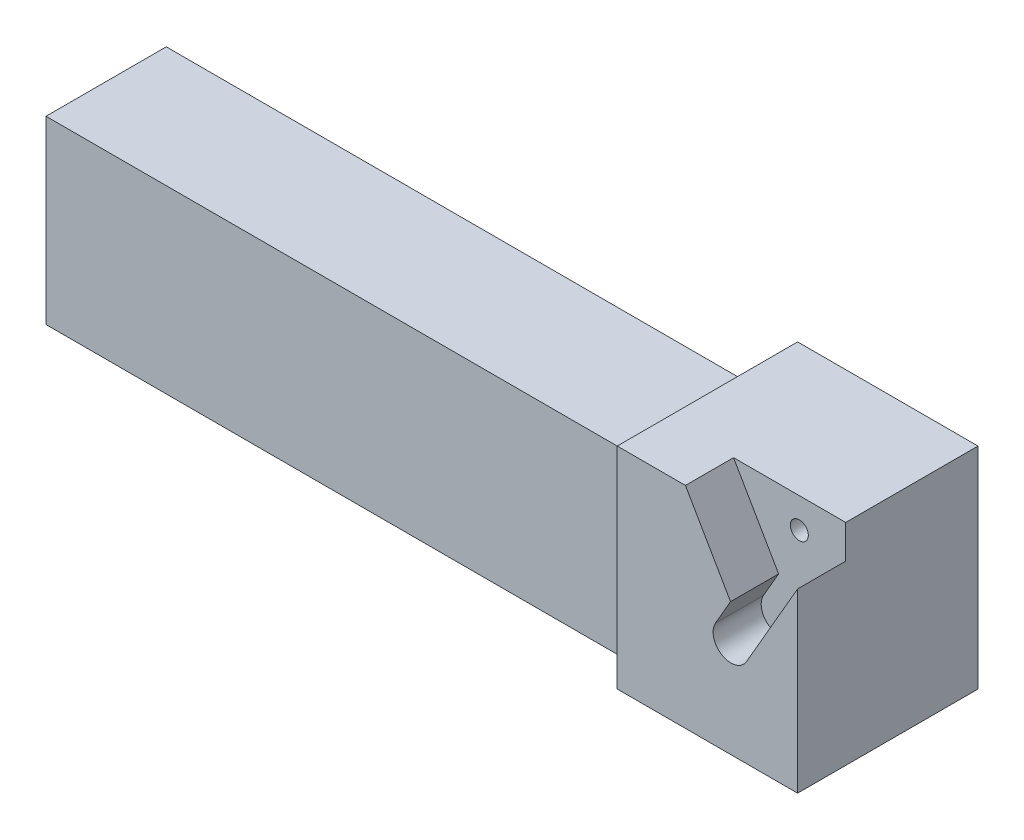
SolidWorks part; units mm, degrees
ref_plane "前视基准面" through (0, 0, 0) normal (0, 0, 1) x (1, 0, 0)
ref_plane "上视基准面" through (0, 0, 0) normal (0, 1, 0) x (1, 0, 0)
ref_plane "右视基准面" through (0, 0, 0) normal (1, 0, 0) x (0, 0, -1)
sketch "草图1" plane through (0, 0, 0) normal (0, 0, 1) x (1, 0, 0)
  line L1 (-45, 15) -> (55, 15)
  line L2 (-45, 15) -> (-45, -15)
  line L3 (-45, -15) -> (55, -15)
  line L4 (55, 15) -> (55, -15)
  point P0 (0, 0)
  dimension "D1" = 100
  dimension "D2" = 30
  dimension "D3" = 55
extrude "凸台-拉伸1" add sketch "草图1" along normal blind 20
sketch "草图2" plane through (55, 0, 0) normal (1, 0, 0) x (0, 0, -1)
  line L10 (-25, -15) -> (5, -15)
  line L14 (-25, -20) -> (5, -20)
  line L15 (5, -20) -> (5, 20)
  line L16 (-25, 20) -> (-25, -20)
  line L17 (5, 20) -> (-25, 20)
  line L19 (5, -15) -> (5, 20)
  line L20 (-25, 20) -> (-25, -15)
  line L21 (5, 20) -> (-25, 20)
  dimension "D1" = 5
extrude "凸台-拉伸2" add sketch "草图2" along normal blind 30
fillet "圆角1" radius 5 3 edges at (55, 15, 10)
sketch "草图3" plane through (0, 0, 25) normal (0, 0, 1) x (1, 0, 0)
  line L0 (73.8428, 7.0096) -> (66.3428, 20)
  line L2 (85, 20) -> (55, 20) construction
  line L3 (78.3561, 2.9168) -> (85, 14.4244)
  line L5 (73.8428, 7.0096) -> (71.3428, 2.6795)
  line L6 (78.3561, 2.9168) -> (76.5, -0.298)
  line L7 (85, 20) -> (85, -15) construction
  line L8 (66.3428, 20) -> (85, 20)
  line L9 (85, 20) -> (85, 14.4244)
  arc A0 (71.3428, 2.6795) -> (76.5, -0.298) centre (73.9214, 1.1907) ccw
  dimension "D1" = 15
  dimension "D2" = 5
  dimension "D3" = 17
  dimension "D4" = 60
  dimension "D5" = 60
extrude "切除-拉伸1" cut sketch "草图3" against normal blind 8
sketch "草图4" plane through (0, 0, 17) normal (0, 0, 1) x (1, 0, 0)
  line L0 (66.3428, 20) -> (77.2809, 1.0546) construction
  line L1 (76.5, -0.298) -> (85, 14.4244) construction
  line L2 (77.2809, 1.0546) -> (77.2809, 36.8047) construction
  circle A0 centre (77.2809, 15.0146) radius 1.5
  dimension "D1" = 3
  dimension "D2" = 13.96
extrude "切除-拉伸2" cut sketch "草图4" against normal through all
cosmetic thread "装饰螺纹线1" parameters "D1"=18, "D2"=9
